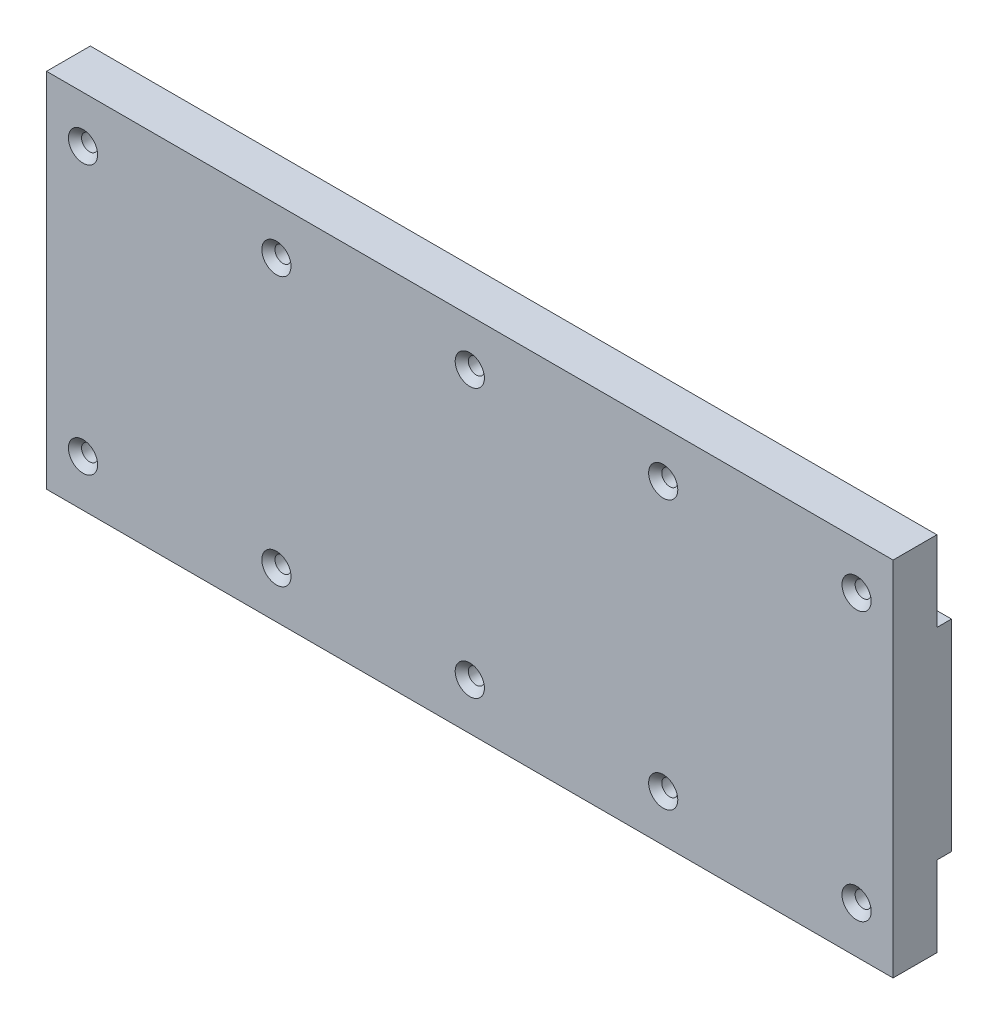
SolidWorks part; units mm, degrees
ref_plane "前基準面" through (0, 0, 0) normal (0, 0, 1) x (1, 0, 0)
ref_plane "上基準面" through (0, 0, 0) normal (0, 1, 0) x (1, 0, 0)
ref_plane "右基準面" through (0, 0, 0) normal (1, 0, 0) x (0, 0, -1)
ref_plane "平面1"
sketch "草圖1" plane through (0, 0, 0) normal (1, 0, 0) x (0, 1, 0)
  line L0 (0, -30) -> (-69, -30)
  line L1 (-69, -30) -> (-69, -40)
  line L2 (-69, -40) -> (69, -40)
  line L3 (69, -40) -> (69, -30)
  line L4 (69, -30) -> (0, -30)
  line L5 (124, 0) -> (-124, 0)
  line L6 (-124, 0) -> (-124, -30)
  line L7 (-124, -30) -> (0, -30)
  line L8 (0, -30) -> (124, -30)
  line L9 (124, -30) -> (124, 0)
  dimension "D1" = 248
  dimension "D2" = 30
  dimension "D3" = 138
  dimension "D4" = 10
extrude "擠出1" add sketch "草圖1" along normal blind 290 and the other way blind 290 contours L3 L4 L0 L1 L2 | L8 L9 L5 L6 L7 L0 L4 region at (0, 0, -35) region at (0, 0, -15)
hole_wizard "孔1" positions "草圖3" profile "草圖2" legacy end condition through all
sketch "草圖3" plane through (0, 0, 0) normal (0, 0, 1) x (1, 0, 0)
  point P1 (-265, 92)
  point P2 (-265, -92)
sketch "草圖2" plane through (-265, 92, 0) normal (1, 0, 0) x (0, -1, 0)
  line L0 (0, 0) -> (0, 40)
  line L1 (0, 40) -> (5.5, 40)
  line L2 (5.5, 40) -> (5.5, 4.5)
  line L3 (5.5, 4.5) -> (10, 0)
  line L4 (10, 0) -> (0, 0)
  line L5 (0, -6.4453) -> (0, 115.525) construction
  line L6 (-5.5, 4.5) -> (-10, 0) construction
  dimension "直徑" = 11
  dimension "深度" = 40
  dimension "錐孔角度1" = 90
  dimension "錐孔直徑1" = 20
ref_plane "平面2" through (0, 0, 0) normal (0, -1, 0) x (-1, 0, 0)
ref_plane "平面3" through (0, 0, 0) normal (0, 0, 1) x (1, 0, 0)
ref_axis "基準軸1" through (-80.9, 0, 0) along (1, 0, 0)
pattern_linear "矩形陣列1" count 5 spacing 132.5 along (1, 0, 0) of "孔1"
